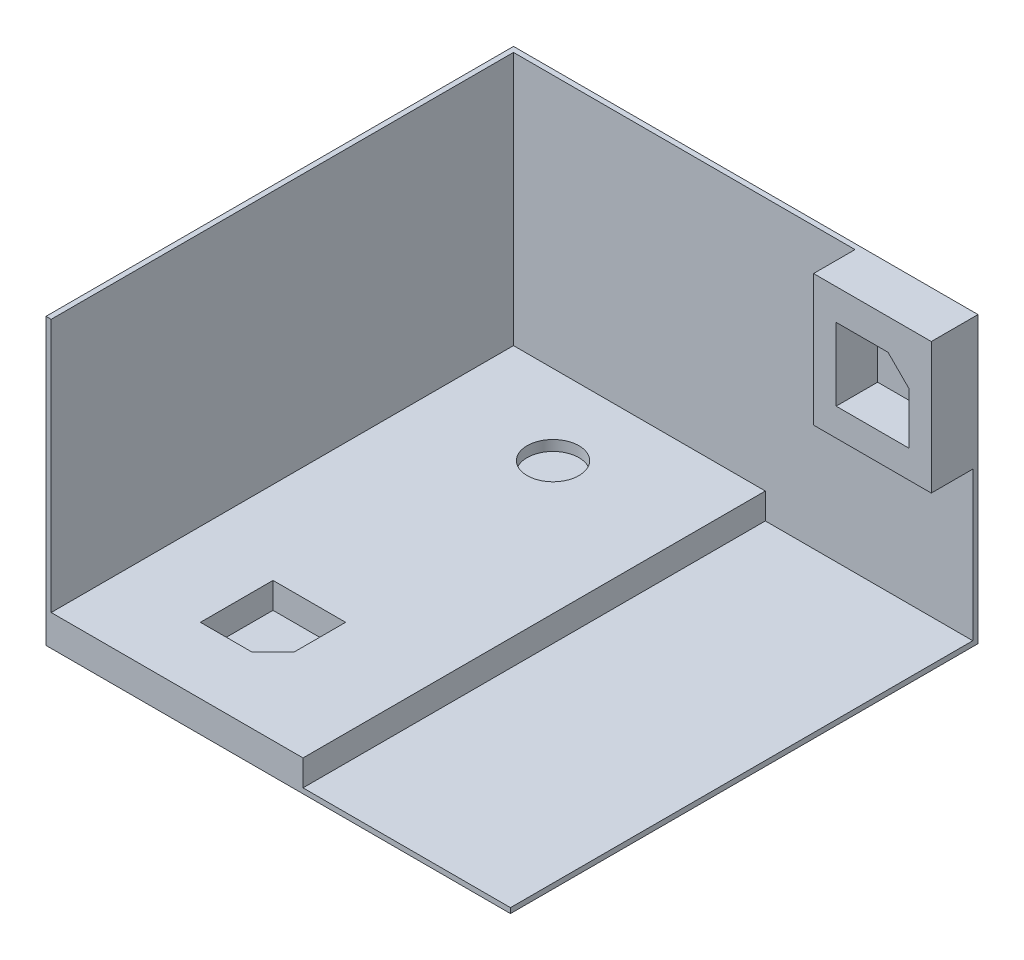
SolidWorks part; units mm, degrees
ref_plane "Front Plane" through (0, 0, 0) normal (0, 0, 1) x (1, 0, 0)
ref_plane "Top Plane" through (0, 0, 0) normal (0, 1, 0) x (1, 0, 0)
ref_plane "Right Plane" through (0, 0, 0) normal (1, 0, 0) x (0, 0, -1)
sketch "Sketch1" plane through (0, 0, 0) normal (0, 1, 0) x (1, 0, 0)
  line L0 (607.1286, 5725.052) -> (607.1286, -5725.0521)
  line L1 (5687.7991, 5725.0521) -> (-5687.7991, 5725.052)
  line L2 (5687.7991, 5725.0521) -> (5687.7991, -5725.052)
  line L3 (5687.7991, -5725.052) -> (-5687.7991, -5725.0521)
  line L4 (-5687.7991, 5725.052) -> (-5687.7991, -5725.0521)
  line L5 (5687.7991, 5725.0521) -> (-5687.7991, -5725.0521) construction
  line L6 (5687.7991, -5725.052) -> (-5687.7991, 5725.052) construction
  line L7 (-1747.7765, -3597.2026) -> (-2255.7765, -4105.2026)
  line L8 (-3525.7765, -2327.2026) -> (-1747.7765, -2327.2026)
  line L9 (-3525.7765, -2327.2026) -> (-3525.7765, -4105.2026)
  line L10 (-3525.7765, -4105.2026) -> (-2255.7765, -4105.2026)
  line L11 (-1747.7765, -2327.2026) -> (-1747.7765, -3597.2026)
  line L12 (-3525.7765, -2327.2026) -> (-2001.7765, -3851.2026) construction
  line L13 (-3525.7765, -4105.2026) -> (-1747.7765, -2327.2026) construction
  line L14 (-5560.7991, -5725.0521) -> (-5560.7991, 5597.2202)
  line L15 (-5560.7991, 5597.2202) -> (5687.7991, 5597.2202)
  line L16 (-2636.7765, 3641.7974) -> (-2636.7765, -3216.2026) construction
  circle A0 centre (-2636.7765, 3641.7974) radius 635
  point P0 (0, 0)
  point P8 (-2636.7765, -3216.2026)
  point P17 (-2001.7765, -3851.2026)
  dimension "D10" = 1270
  dimension "D1" = 11450.1041
  dimension "D2" = 11375.5983
  dimension "D3" = 6294.9277
  dimension "D4" = 1778
  dimension "D5" = 1778
  dimension "D6" = 1270
  dimension "D7" = 1270
  dimension "D9" = 1619.8494
  dimension "D11" = 2083.2547
  dimension "D12" = 3051.0226
  dimension "D13" = 127
extrude "Boss-Extrude1" add sketch "Sketch1" along normal blind 127 contours L15 L0 L3 L2 | L15 L14 L3 L0 A0 L8 L11 L7 L10 L9 | L14 L15 L0 L1 L4 L3 | L0 L15 L2 L1 | L11 L8 L9 L10 L7 | A0 region at (3147.4639, 0, -5661.1361) region at (476.4645, 0, -5661.1361) region at (3147.4639, 0, 63.9159) region at (-2464.9265, 0, -8.8897) region at (-2667.4007, 0, 3185.5785) region at (-2636.7765, 0, -3641.7974)
extrude "Boss-Extrude2" add sketch "Sketch1<3>" along normal blind 762 contours L15 L14 L3 L0 A0 L8 L11 L7 L10 L9 | L14 L15 L0 L1 L4 L3 | L0 L15 L2 L1 region at (3147.4639, 0, -5661.1361) region at (476.4645, 0, -5661.1361) region at (-2464.9265, 0, -8.8897)
sketch "Sketch1<3>" plane through (0, 0, 0) normal (0, 1, 0) x (1, 0, 0) same geometry as "Sketch1"
extrude "Boss-Extrude3" add sketch "Sketch1<4>" along normal blind 6981.2052 contours L0 L15 L2 L1 | L14 L15 L0 L1 L4 L3 region at (3147.4639, 0, -5661.1361) region at (476.4645, 0, -5661.1361)
sketch "Sketch1<4>" plane through (0, 0, 0) normal (0, 1, 0) x (1, 0, 0) same geometry as "Sketch1"
extrude "Boss-Extrude5" add sketch "Sketch1<6>" along normal offset from surface (508 mm away) 254 contours A0 region at (-2636.7765, 0, -3641.7974) up to face at (-2636.7765, 762, -3006.7974)
sketch "Sketch1<6>" plane through (0, 0, 0) normal (0, 1, 0) x (1, 0, 0) same geometry as "Sketch1"
sketch "Sketch2" plane through (0, 0, -5597.2202) normal (0, 0, 1) x (1, 0, 0)
  line L0 (5687.7991, 0) -> (-5687.7991, 0) construction
  line L1 (5687.7991, 6981.2052) -> (2804.1397, 6981.2052)
  line L2 (5687.7991, 6981.2052) -> (5687.7991, 3766.5254)
  line L3 (5687.7991, 3766.5254) -> (2804.1397, 3766.5254)
  line L4 (2804.1397, 6981.2052) -> (2804.1397, 3766.5254)
  line L5 (4627.6235, 6223) -> (5135.6235, 5715)
  line L6 (5135.6235, 4445) -> (3357.6235, 4445)
  line L7 (5135.6235, 4445) -> (5135.6235, 5715)
  line L8 (4627.6235, 6223) -> (3357.6235, 6223)
  line L9 (3357.6235, 4445) -> (3357.6235, 6223)
  line L10 (5135.6235, 4445) -> (3357.6235, 6223) construction
  line L11 (4881.6235, 5969) -> (3357.6235, 4445) construction
  point P7 (4246.6235, 5334)
  point P14 (4881.6235, 5969)
  dimension "D1" = 2883.6595
  dimension "D2" = 3766.5254
  dimension "D3" = 678.4746
  dimension "D4" = 553.4838
  dimension "D5" = 1270
  dimension "D6" = 1778
extrude "Boss-Extrude6" add sketch "Sketch2" along normal blind 1016
equation "\"dfl.hk\"=4.80136"
